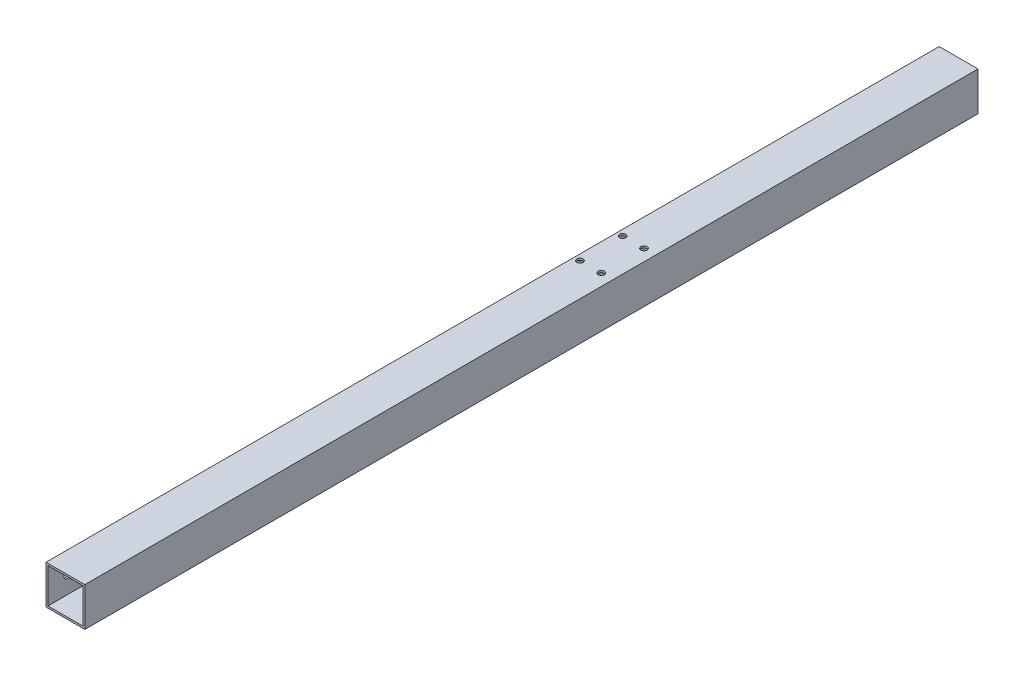
SolidWorks part; units mm, degrees
ref_plane "前视基准面" through (0, 0, 0) normal (0, 0, 1) x (1, 0, 0)
ref_plane "上视基准面" through (0, 0, 0) normal (0, 1, 0) x (1, 0, 0)
ref_plane "右视基准面" through (0, 0, 0) normal (1, 0, 0) x (0, 0, -1)
sketch "草图1" plane through (0, 0, 0) normal (0, 0, 1) x (1, 0, 0)
  line L1 (-10, 10) -> (10, 10)
  line L2 (-10, 10) -> (-10, -10)
  line L3 (-10, -10) -> (10, -10)
  line L4 (10, 10) -> (10, -10)
  line L5 (-10, 10) -> (10, -10) construction
  line L6 (-10, -10) -> (10, 10) construction
  line L7 (-9, 9) -> (9, 9)
  line L8 (-9, 9) -> (-9, -9)
  line L9 (-9, -9) -> (9, -9)
  line L10 (9, 9) -> (9, -9)
  line L11 (-9, 9) -> (9, -9) construction
  line L12 (-9, -9) -> (9, 9) construction
  point P0 (0, 0)
  point P6 (0, 0)
  dimension "D1" = 20
  dimension "D2" = 20
  dimension "D3" = 18
  dimension "D4" = 18
extrude "凸台-拉伸1" add sketch "草图1" along normal blind 460
sketch "草图2" plane through (-10, 0, 0) normal (-1, 0, 0) x (0, 0, 1)
  circle A0 centre (10, 0) radius 1.8
  dimension "D1" = 3.6
extrude "切除-拉伸1" cut sketch "草图2" against normal blind 3
sketch "草图3" plane through (-10, 0, 0) normal (-1, 0, 0) x (0, 0, 1)
  line L1 (0, 10) -> (0, -10) construction
  circle A0 centre (198, 0) radius 1.8
  dimension "D1" = 198
extrude "切除-拉伸2" cut sketch "草图3" against normal blind 3
sketch "草图5" plane through (-10, 0, 0) normal (-1, 0, 0) x (0, 0, 1)
  line L0 (460, 10) -> (460, -10) construction
  circle A0 centre (450, 0) radius 1.8
  dimension "D1" = 10
extrude "切除-拉伸3" cut sketch "草图5" against normal blind 3
sketch "草图6" plane through (-10, 0, 0) normal (-1, 0, 0) x (0, 0, 1)
  line L0 (460, 10) -> (460, -10) construction
  circle A0 centre (262, 0) radius 1.8
  dimension "D1" = 198
extrude "切除-拉伸4" cut sketch "草图6" against normal blind 10
sketch "草图7" plane through (0, 10, 0) normal (0, 1, 0) x (1, 0, 0)
  circle A0 centre (4, -166) radius 1.6
  circle A1 centre (-7, -166) radius 1.6
  circle A2 centre (4, -188) radius 1.6
  circle A3 centre (-7, -188) radius 1.6
extrude "切除-拉伸5" cut sketch "草图7" against normal blind 20
